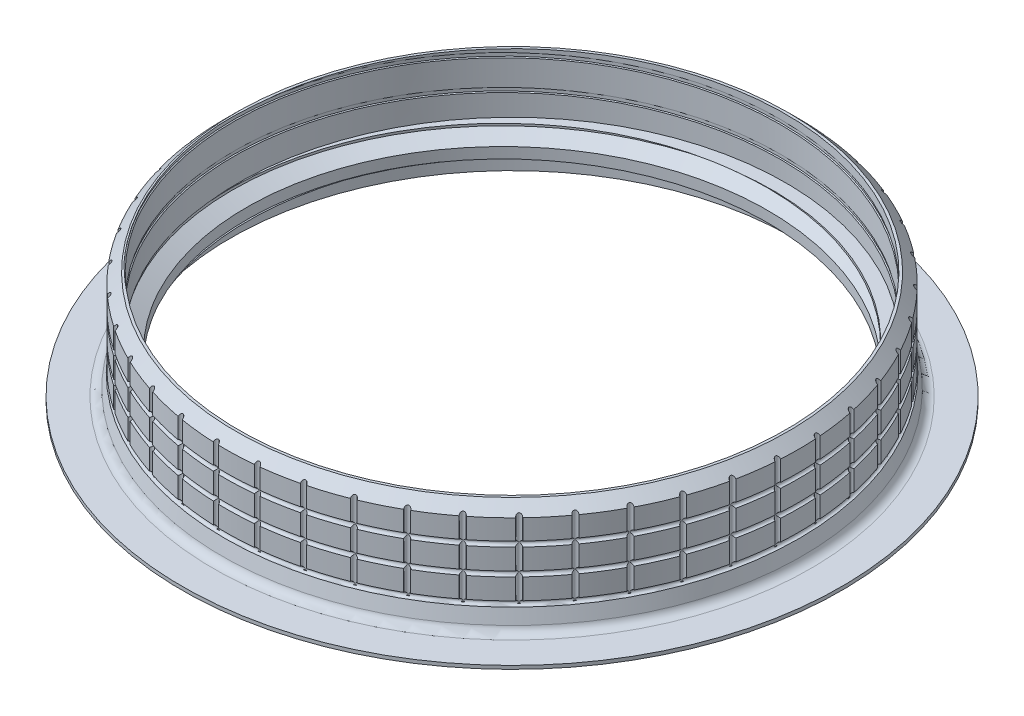
SolidWorks part; units mm, degrees
note: '?' marks a value the reader was unsure of.
ref_plane "Спереди" through (0, 0, 0) normal (0, 0, 1) x (1, 0, 0)
ref_plane "Сверху" through (0, 0, 0) normal (0, 1, 0) x (1, 0, 0)
ref_plane "Справа" through (0, 0, 0) normal (1, 0, 0) x (0, 0, -1)
sketch "Эскиз1" plane through (0, 0, 0) normal (0, 0, 1) x (1, 0, 0)
  line L0 (0, 0) -> (0, 12.8105) construction
  line L1 (-38.25, 0) -> (-32.65, 0)
  line L2 (-32.65, 0) -> (-32.65, 1.8)
  line L3 (-32.65, 1.8) -> (-30.25, 1.8)
  line L4 (-30.25, 1.8) -> (-30.25, 6)
  line L5 (-31.75, 12.9) -> (-33.25, 12.9)
  line L6 (-33.25, 12.9) -> (-33.25, 3)
  line L7 (-34.6455, 0.4) -> (-38.25, 0.4)
  line L8 (-38.25, 0.4) -> (-38.25, 0)
  line L10 (-33.25, 3) -> (-33.6711, 1.1751)
  line L18 (-30.25, 6) -> (-31.75, 6)
  line L19 (-31.75, 12.9) -> (-31.75, 6)
  arc A0 (-34.6455, 0.4) -> (-33.6711, 1.1751) centre (-34.6455, 1.4) ccw
  point P11 (-33.85, 0.4)
  dimension "D11" = 1
  dimension "D1" = 66.5
  dimension "D2" = 5
  dimension "D4" = 0.4
  dimension "D3" = 12.5
  dimension "D7" = 1.2
  dimension "D8" = 1.2
  dimension "D9" = 1.8
  dimension "D6" = 60.5
  dimension "D10" = 2.4
  dimension "D12" = 1.5
  dimension "D5" = 6
revolve "Повернуть1" add sketch "Эскиз1" angle 360 about L0
chamfer "Upper faсet" distance 1.2 angle 45 1 edges at (0, 12.9, -33.25)
sketch "Эскиз4" plane through (0, 0, 0) normal (0, 0, 1) x (1, 0, 0)
  line L0 (-33.25, 11.7) -> (-33.25, 3) construction
  line L1 (0, 0) -> (0, 15.1618) construction
  circle A0 centre (-33.25, 3.0538) radius 0.3
  circle A1 centre (-33.25, 6.0538) radius 0.3
  circle A2 centre (-33.25, 9.0538) radius 0.3
  dimension "D1" = 3
  dimension "D2" = 0.6
revolve "Grip" cut sketch "Эскиз4" angle 360 about L1
sketch "Эскиз5" plane through (0, 12.9, 0) normal (0, 1, 0) x (1, 0, 0)
  circle A0 centre (0, 0) radius 33.25 construction
  circle A1 centre (-33.25, 0) radius 0.3
  circle A2 centre (-32.9264, 4.6275) radius 0.3
  circle A3 centre (-31.962, 9.1649) radius 0.3
  circle A4 centre (-30.3754, 13.524) radius 0.3
  circle A5 centre (-28.1976, 17.6198) radius 0.3
  circle A6 centre (-25.471, 21.3727) radius 0.3
  circle A7 centre (-22.2486, 24.7096) radius 0.3
  circle A8 centre (-18.5932, 27.5655) radius 0.3
  circle A9 centre (-14.5758, 29.8849) radius 0.3
  circle A10 centre (-10.2748, 31.6226) radius 0.3
  circle A11 centre (-5.7738, 32.7449) radius 0.3
  circle A12 centre (-1.1604, 33.2297) radius 0.3
  circle A13 centre (3.4756, 33.0679) radius 0.3
  circle A14 centre (8.0439, 32.2623) radius 0.3
  circle A15 centre (12.4557, 30.8289) radius 0.3
  circle A16 centre (16.625, 28.7953) radius 0.3
  circle A17 centre (20.4707, 26.2014) radius 0.3
  circle A18 centre (23.918, 23.0974) radius 0.3
  circle A19 centre (26.8998, 19.5439) radius 0.3
  circle A20 centre (29.358, 15.6099) radius 0.3
  circle A21 centre (31.2448, 11.3722) radius 0.3
  circle A22 centre (32.5234, 6.9131) radius 0.3
  circle A23 centre (33.169, 2.3194) radius 0.3
  circle A24 centre (33.169, -2.3194) radius 0.3
  circle A25 centre (32.5234, -6.9131) radius 0.3
  circle A26 centre (31.2448, -11.3722) radius 0.3
  circle A27 centre (29.358, -15.6099) radius 0.3
  circle A28 centre (26.8998, -19.5439) radius 0.3
  circle A29 centre (23.918, -23.0974) radius 0.3
  circle A30 centre (20.4707, -26.2014) radius 0.3
  circle A31 centre (16.625, -28.7953) radius 0.3
  circle A32 centre (12.4557, -30.8289) radius 0.3
  circle A33 centre (8.0439, -32.2623) radius 0.3
  circle A34 centre (3.4756, -33.0679) radius 0.3
  circle A35 centre (-1.1604, -33.2297) radius 0.3
  circle A36 centre (-5.7738, -32.7449) radius 0.3
  circle A37 centre (-10.2748, -31.6226) radius 0.3
  circle A38 centre (-14.5758, -29.8849) radius 0.3
  circle A39 centre (-18.5932, -27.5655) radius 0.3
  circle A40 centre (-22.2486, -24.7096) radius 0.3
  circle A41 centre (-25.471, -21.3727) radius 0.3
  circle A42 centre (-28.1976, -17.6198) radius 0.3
  circle A43 centre (-30.3754, -13.524) radius 0.3
  circle A44 centre (-31.962, -9.1649) radius 0.3
  circle A45 centre (-32.9264, -4.6275) radius 0.3
  dimension "D2" = 66.5
  dimension "D3" = 0.6
  dimension "D1" = 45
extrude "Вырез-Вытянуть1" cut sketch "Эскиз5" against normal blind 10
thread "Резьба1" pitch 3 start angle 0, offset 6, length 20, pitch 3.5, diameter 60.5
ref_plane "Плоскость1" through (30.25, -4.2, 0) normal (0, 0, 1) x (1, 0, 0)
sketch "Профиль резьбы1" plane through (30.25, -4.2, 0) normal (0, 0, 1) x (1, 0, 0)
  line L0 (0, 0) -> (0, 3) construction
  line L1 (0, 0) -> (1.6238, 0.9375)
  line L2 (1.6238, 0.9375) -> (1.6238, 1.3125)
  line L3 (1.6238, 1.3125) -> (0, 2.25)
  line L4 (1.6238, 1.125) -> (0, 1.125) construction
  line L11 (0, 0) -> (0, 2.25)
  point P2 (0, 0)
  dimension "Pitch" = 3
  dimension "Profile_Angle" = 60
  dimension "Profile_Land" = 0.375
  dimension "Profile_Height" = 1.6238
ref_axis "Ось1" through (0, 15.426, 0) along (0, -1, 0)?
equation "\"HoleDiameter\"=67.5"
equation "\"HoleDiameterError\"=1"
equation "\"InsertInletDiameter\"=\"HoleDiameter\" - \"HoleDiameterError\""
equation "\"D1@Эскиз1\"=\"InsertInletDiameter\""
equation "\"InsertRimWidth\"=5"
equation "\"D2@Эскиз1\"=\"InsertRimWidth\""
equation "\"InsertInletThickness\"=6"
equation "\"InsertInletHeight\"=12.5"
equation "\"CapRimWidth\"=2"
equation "\"InsertRimThickness\"=0.4"
equation "\"D4@Эскиз1\"=\"InsertRimThickness\""
equation "\"D3@Эскиз1\"=\"InsertInletHeight\""
equation "\"CapRimThickness\"=1.2"
equation "\"D7@Эскиз1\"=\"CapRimThickness\""
equation "\"D8@Эскиз1\"=\"CapRimThickness\""
equation "\"D9@Эскиз1\"=\"CapRimThickness\" + 0.6"
equation "\"D1@Upper faсet\" = \"InsertInletThickness\" / 5"
equation "\"JunctionDiameter\"=\"InsertInletDiameter\" - \"InsertInletThickness\""
equation "\"D6@Эскиз1\"=\"JunctionDiameter\""
equation "\"CapDepth\"=(\"InsertRimThickness\"+\"InsertInletHeight\")*0.7"
equation "\"D10@Эскиз1\"= \"CapRimWidth\" + ( \"RimJunctionError\" / 2 )"
equation "\"ThreadDepth\"=0.766391"
equation "\"D2@Эскиз5\"=\"InsertInletDiameter\""
equation "\"RimJunctionError\"=0.8"
equation "\"ThreadJunctionError\"=0.4"
equation "\"DriverSlotsDistance\"=40"
